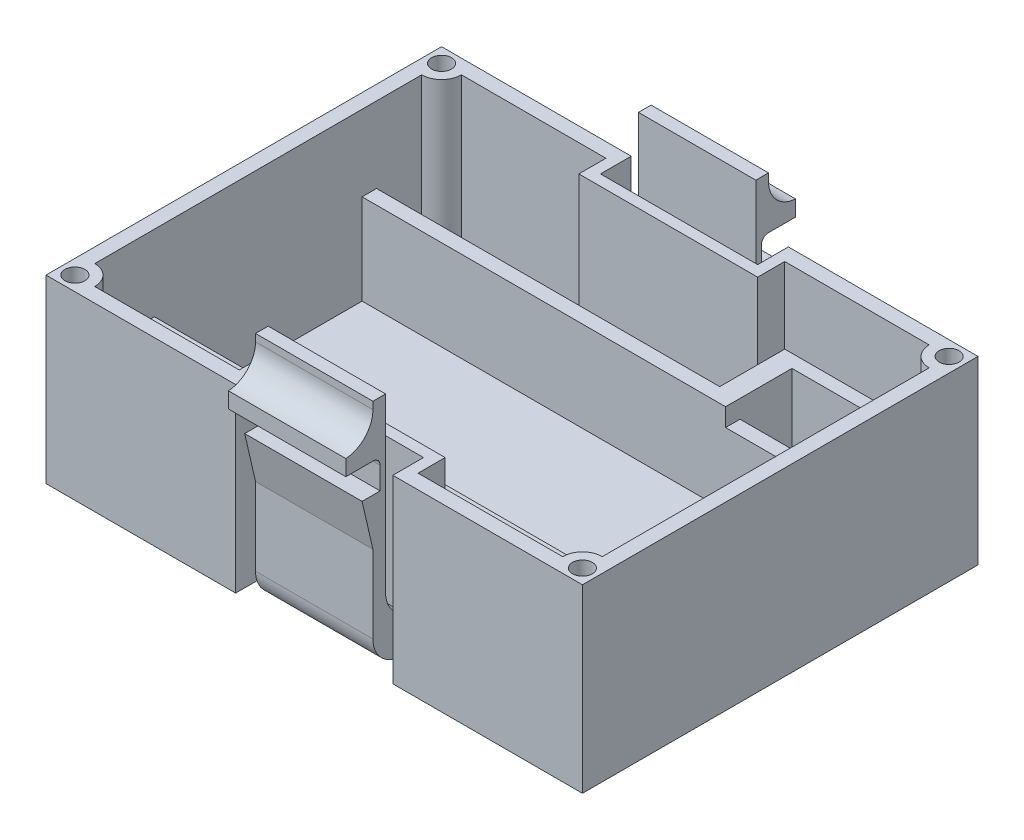
SolidWorks part; units mm, degrees
ref_plane "Front Plane" through (0, 0, 0) normal (0, 0, 1) x (1, 0, 0)
ref_plane "Top Plane" through (0, 0, 0) normal (0, 1, 0) x (1, 0, 0)
ref_plane "Right Plane" through (0, 0, 0) normal (1, 0, 0) x (0, 0, -1)
sketch "Sketch1" plane through (0, 0, 0) normal (0, 1, 0) x (1, 0, 0)
  line L0 (-38.4, 43.8) -> (-38.4, 40.4)
  line L1 (0, 0) -> (-21, 0)
  line L2 (0, 0) -> (0, 43.8)
  line L3 (0, 43.8) -> (-21, 43.8)
  line L4 (-59.4, 0) -> (-59.4, 43.8)
  line L5 (-21, 43.8) -> (-21, 40.4)
  line L6 (-38.4, 3.4) -> (-21, 3.4)
  line L7 (-38.4, 40.4) -> (-21, 40.4)
  line L8 (-38.4, 43.8) -> (-59.4, 43.8)
  line L9 (-38.4, 0) -> (-59.4, 0)
  line L10 (-21, 3.4) -> (-21, 0)
  line L11 (-38.4, 3.4) -> (-38.4, 0)
  dimension "D1" = 59.4
  dimension "D2" = 43.8
  dimension "D3" = 43.8
  dimension "D4" = 21
  dimension "D5" = 21
  dimension "D6" = 37
  dimension "D7" = 3.4
extrude "Boss-Extrude1" add sketch "Sketch1" along normal blind 20
sketch "Sketch2" plane through (0, 20, 0) normal (0, 1, 0) x (1, 0, 0)
  line L0 (-59.4, 43.8) -> (-59.4, 0) construction
  line L1 (-57.8, 42.2) -> (-39.6, 42.2)
  line L2 (-57.8, 42.2) -> (-57.8, 1.6)
  line L3 (-57.8, 1.6) -> (-39.6, 1.6)
  line L4 (-1.6, 42.2) -> (-1.6, 1.6)
  line L5 (0, 0) -> (0, 43.8) construction
  line L6 (-38.4, 43.8) -> (-59.4, 43.8) construction
  line L7 (-59.4, 0) -> (-38.4, 0) construction
  line L8 (-39.6, 1.6) -> (-39.6, 4.6)
  line L9 (-38.4, 40.4) -> (-38.4, 43.8) construction
  line L10 (-19.8, 42.2) -> (-19.8, 39.2)
  line L11 (-21, 43.8) -> (-21, 40.4) construction
  line L12 (-39.6, 39.2) -> (-19.8, 39.2)
  line L13 (-39.6, 4.6) -> (-19.8, 4.6)
  line L14 (-38.4, 3.4) -> (-21, 3.4) construction
  line L15 (-21, 40.4) -> (-38.4, 40.4) construction
  line L16 (-19.8, 42.2) -> (-1.6, 42.2)
  line L17 (-19.8, 1.6) -> (-1.6, 1.6)
  line L18 (-19.8, 4.6) -> (-19.8, 1.6)
  line L19 (-39.6, 39.2) -> (-39.6, 42.2)
  dimension "D1" = 1.6
  dimension "D2" = 1.6
  dimension "D3" = 1.6
  dimension "D4" = 1.6
  dimension "D5" = 1.2
  dimension "D6" = 1.2
  dimension "D7" = 1.2
  dimension "D8" = 1.2
extrude "Cut-Extrude1" cut sketch "Sketch2" against normal blind 18.4
sketch "Sketch3" plane through (0, 1.6, 0) normal (0, 1, 0) x (1, 0, 0)
  line L0 (0, 43.8) -> (-21, 43.8) construction
  line L1 (-1.6, 39.3) -> (-16.1, 39.3)
  line L2 (-1.6, 39.3) -> (-1.6, 36.45)
  line L3 (-1.6, 36.45) -> (-16.1, 36.45)
  line L4 (-16.1, 39.3) -> (-16.1, 36.45)
  line L5 (0, 0) -> (0, 43.8) construction
  dimension "D1" = 4.5
  dimension "D2" = 2.85
  dimension "D3" = 14.5
  dimension "D4" = 1.6
extrude "Cut-Extrude2" cut sketch "Sketch3" against normal blind 18.4
sketch "Sketch4" plane through (0, 0, 0) normal (0, -1, 0) x (1, 0, 0)
  line L1 (-36.2, 0) -> (-23.2, 0)
  line L2 (-36.2, 0) -> (-36.2, -1.4)
  line L4 (-23.2, 0) -> (-23.2, -1.4)
  line L5 (-21, -40.4) -> (-38.4, -40.4) construction
  line L7 (-23.2, -42.4) -> (-23.2, -43.8)
  line L8 (-23.2, -43.8) -> (-36.2, -43.8)
  line L9 (-36.2, -42.4) -> (-36.2, -43.8)
  line L10 (-21, -43.8) -> (-21, -40.4) construction
  line L11 (-21, -3.4) -> (-21, 0) construction
  line L13 (-23.2, -1.4) -> (-36.2, -1.4)
  line L14 (-23.2, -42.4) -> (-36.2, -42.4)
  line L17 (-38.4, -3.4) -> (-21, -3.4) construction
  dimension "D1" = 13
  dimension "D2" = 13
  dimension "D3" = 2.2
  dimension "D4" = 2.2
  dimension "D5" = 1.4
  dimension "D6" = 2
  dimension "D7" = 1.4
  dimension "D8" = 2
extrude "Boss-Extrude2" add sketch "Sketch4" against normal blind 22 separate body
sketch "Sketch5" plane through (0, 0, 0) normal (0, -1, 0) x (-1, 0, 0)
  line L0 (36.2, 0) -> (36.2, 3.4)
  line L1 (36.2, 43.8) -> (23.2, 43.8)
  line L2 (23.2, 43.8) -> (23.2, 40.4)
  line L3 (23.2, 0) -> (36.2, 0)
  line L4 (36.2, 3.4) -> (23.2, 3.4)
  line L5 (38.4, 3.4) -> (21, 3.4) construction
  line L6 (23.2, 40.4) -> (36.2, 40.4)
  line L7 (21, 40.4) -> (38.4, 40.4) construction
  line L8 (36.2, 40.4) -> (36.2, 43.8)
  line L9 (23.2, 3.4) -> (23.2, 0)
extrude "Boss-Extrude3" add sketch "Sketch5" against normal blind 4
fillet "Fillet1" radius 3.2 2 edges at (-29.7, 0, -43.8) (-29.7, 0, 0)
fillet "Fillet2" radius 3.2 2 edges at (-29.7, 4, -1.4) (-29.7, 4, -42.4)
sketch "Sketch7" plane through (-23.2, 0, 0) normal (1, 0, 0) x (0, 0, -1)
  line L0 (0, 20) -> (0, 0) construction
  line L1 (-1.2, 17) -> (0, 17)
  line L4 (0, 17) -> (0, 11.8)
  line L6 (43.8, 20) -> (43.8, 0) construction
  line L8 (43.8, 11.8) -> (43.8, 17)
  line L9 (43.8, 17) -> (45, 17)
  line L11 (0, 11.8) -> (-1.2, 17)
  line L12 (43.8, 11.8) -> (45, 17)
  line L13 (0, 0) -> (43.8, 0) construction
  line L14 (0, 22) -> (0, 3.2) construction
  line L15 (0, 22) -> (-3, 22)
  line L16 (1.4, 22) -> (1.4, 20.26)
  line L17 (1.4, 20.26) -> (-3, 20.26)
  line L18 (-3, 22) -> (-3, 20.26)
  line L19 (43.8, 22) -> (46.8, 22)
  line L20 (42.4, 22) -> (42.4, 20.26)
  line L21 (42.4, 20.26) -> (46.8, 20.26)
  line L22 (46.8, 22) -> (46.8, 20.26)
  line L23 (43.8, 22) -> (43.8, 3.2) construction
  line L26 (1.4, 22) -> (1.4, 26)
  line L27 (1.4, 26) -> (0, 26)
  line L28 (0, 22) -> (0, 26)
  line L30 (42.4, 22) -> (42.4, 26)
  line L31 (42.4, 26) -> (43.8, 26)
  line L32 (43.8, 22) -> (43.8, 26)
  dimension "D1" = 11.8
  dimension "D2" = 11.8
  dimension "D3" = 5.2
  dimension "D4" = 5.2
  dimension "D5" = 1.2
  dimension "D6" = 1.2
  dimension "D7" = 3
  dimension "D8" = 3
  dimension "D9" = 1.74
  dimension "D10" = 1.74
  dimension "D11" = 4
extrude "Boss-Extrude4" add sketch "Sketch7" against normal blind 13
sketch "Sketch8" plane through (-23.2, 0, 0) normal (1, 0, 0) x (0, 0, -1)
  line L1 (0, 17) -> (0.8, 17)
  line L2 (0, 17) -> (0, 20.26)
  line L3 (0, 20.26) -> (0.8, 20.26)
  line L4 (0.8, 17) -> (0.8, 20.26)
  line L5 (43.8, 17) -> (43, 17)
  line L6 (43.8, 17) -> (43.8, 20.26)
  line L7 (43.8, 20.26) -> (43, 20.26)
  line L8 (43, 17) -> (43, 20.26)
  dimension "D1" = 0.8
  dimension "D2" = 0.8
  dimension "D3" = 3.26
  dimension "D4" = 3.26
extrude "Cut-Extrude3" cut sketch "Sketch8" against normal blind 13
fillet "Fillet3" radius 3.2 2 edges at (-29.7, 22, 0) (-29.7, 22, -43.8)
fillet "Fillet4" radius 0.8 2 edges at (-29.7, 20.26, -43) (-29.7, 20.26, -0.8)
sketch "Sketch9" plane through (0, 1.6, 0) normal (0, 1, 0) x (1, 0, 0)
  line L0 (-57.8, 42.2) -> (-57.8, 1.6) construction
  line L1 (-57.8, 35) -> (-19.8, 35)
  line L2 (-57.8, 35) -> (-57.8, 33.4)
  line L3 (-57.8, 33.4) -> (-1.6, 33.4)
  line L4 (-1.6, 35) -> (-1.6, 33.4)
  line L5 (-1.6, 1.6) -> (-1.6, 42.2) construction
  line L6 (-1.6, 1.6) -> (-1.6, 36.45) construction
  line L7 (-1.6, 8.8) -> (-57.8, 8.8)
  line L8 (-1.6, 8.8) -> (-1.6, 10.4)
  line L9 (-1.6, 10.4) -> (-57.8, 10.4)
  line L10 (-57.8, 8.8) -> (-57.8, 10.4)
  line L11 (-39.6, 42.2) -> (-57.8, 42.2) construction
  line L13 (-1.6, 40.75) -> (-17.55, 40.75)
  line L18 (-1.6, 39.3) -> (-16.1, 39.3) construction
  line L19 (-17.55, 35) -> (-17.55, 40.75)
  line L20 (-16.1, 39.3) -> (-16.1, 36.45) construction
  line L21 (-19.8, 39.2) -> (-19.8, 35)
  line L22 (-1.6, 40.75) -> (-1.6, 42.2)
  line L23 (-1.6, 42.2) -> (-19.8, 42.2)
  line L24 (-19.8, 42.2) -> (-19.8, 39.2)
  line L25 (-17.55, 35) -> (-1.6, 35)
  dimension "D1" = 23
  dimension "D2" = 1.6
  dimension "D3" = 1.6
  dimension "D4" = 7.2
  dimension "D5" = 1.45
  dimension "D6" = 1.45
extrude "Boss-Extrude5" add sketch "Sketch9" along normal blind 10
sketch "Sketch11" plane through (0, 1.6, 0) normal (0, 1, 0) x (1, 0, 0)
  line L0 (-55.6, 1.6) -> (-57.8, 1.6)
  line L1 (-57.8, 1.6) -> (-57.8, 3.8)
  line L2 (-57.8, 40) -> (-57.8, 42.2)
  line L3 (-57.8, 42.2) -> (-55.6, 42.2)
  line L4 (-1.6, 42.2) -> (-1.6, 40)
  line L5 (-1.6, 42.2) -> (-3.8, 42.2)
  line L6 (-1.6, 1.6) -> (-1.6, 3.8)
  line L7 (-1.6, 1.6) -> (-3.8, 1.6)
  line L8 (-39.6, 42.2) -> (-57.8, 42.2) construction
  line L9 (-38.4, 43.8) -> (-59.4, 43.8) construction
  arc A0 (-57.8, 41.1) -> (-56.7, 42.2) centre (-57.8, 42.2) ccw
  arc A1 (-56.7, 1.6) -> (-57.8, 2.7) centre (-57.8, 1.6) ccw
  arc A2 (-1.6, 2.7) -> (-2.7, 1.6) centre (-1.6, 1.6) ccw
  arc A3 (-2.7, 42.2) -> (-1.6, 41.1) centre (-1.6, 42.2) ccw
  arc A4 (-57.8, 40) -> (-55.6, 42.2) centre (-57.8, 42.2) ccw
  arc A5 (-3.8, 42.2) -> (-1.6, 40) centre (-1.6, 42.2) ccw
  arc A6 (-55.6, 1.6) -> (-57.8, 3.8) centre (-57.8, 1.6) ccw
  arc A7 (-1.6, 3.8) -> (-3.8, 1.6) centre (-1.6, 1.6) ccw
  line M3 (-57.8, 8.8) -> (-57.8, 1.6)
  dimension "D1" = 4.4
sketch "Sketch13" plane through (0, 11.6, 0) normal (0, 1, 0) x (1, 0, 0)
  line L1 (-17.55, 35) -> (-1.6, 35)
  line L2 (-17.55, 35) -> (-17.55, 33.4)
  line L3 (-17.55, 33.4) -> (-1.6, 33.4)
  line L4 (-1.6, 35) -> (-1.6, 33.4)
extrude "Cut-Extrude6" cut sketch "Sketch13" against normal blind 2
extrude "Boss-Extrude6" add sketch "Sketch11" along normal blind 18.4 contours L2 A4 L3 A0 | L0 A6 A1 M3 | L5 A5 L4 A3 | A7 L7 L6 region at (-56.7107, 1.6, -2.6893) region at (-56.7107, 1.6, -41.1107) region at (-2.6893, 1.6, -41.1107)
sketch "Sketch12" plane through (0, 20, 0) normal (0, 1, 0) x (1, 0, 0)
  circle A0 centre (-57.8, 42.2) radius 1.1
  circle A1 centre (-57.8, 1.6) radius 1.1
  circle A2 centre (-1.6, 1.6) radius 1.1
  circle A3 centre (-1.6, 42.2) radius 1.1
extrude "Cut-Extrude5" cut sketch "Sketch12" against normal blind 18.4
sketch "Sketch14" plane through (0, 1.6, 0) normal (0, 1, 0) x (1, 0, 0)
  line L1 (-17.55, 40.75) -> (-1.6, 40.75)
  line L2 (-17.55, 40.75) -> (-17.55, 35)
  line L3 (-17.55, 35) -> (-1.6, 35)
  line L4 (-1.6, 40.75) -> (-1.6, 35)
extrude "Cut-Extrude7" cut sketch "Sketch14" along normal blind 10
